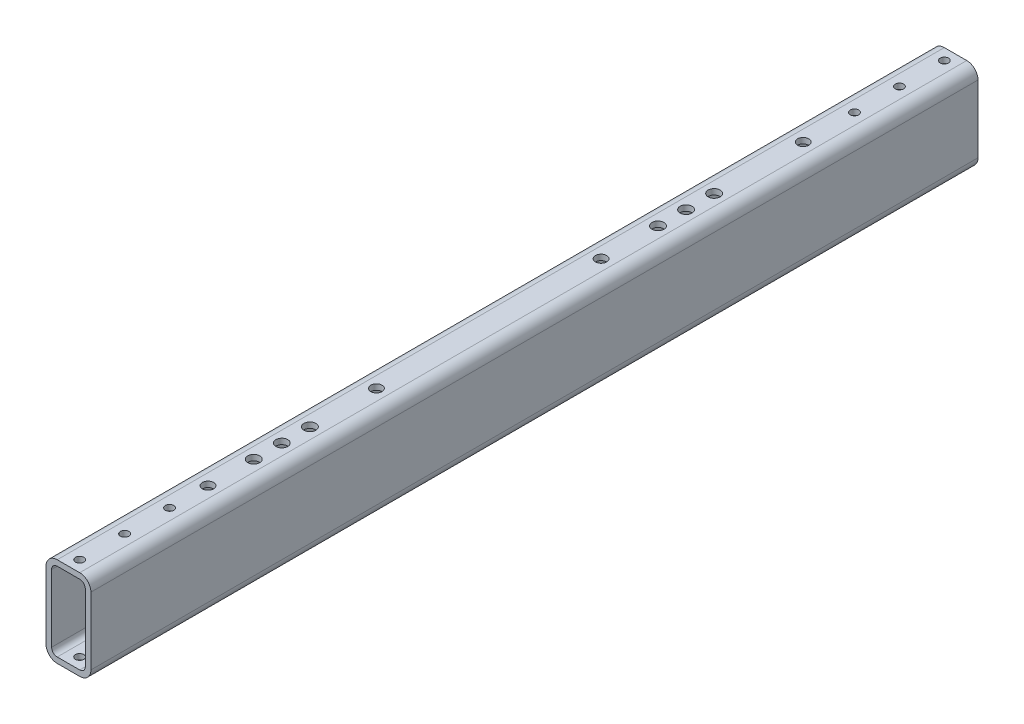
SolidWorks part; units mm, degrees
material "6061-T6 (SS)"
ref_plane "Front Plane" through (0, 0, 0) normal (0, 0, 1) x (1, 0, 0)
ref_plane "Top Plane" through (0, 0, 0) normal (0, 1, 0) x (1, 0, 0)
ref_plane "Right Plane" through (0, 0, 0) normal (1, 0, 0) x (0, 0, -1)
sketch "Sketch1" plane through (0, 0, 0) normal (0, 0, 1) x (1, 0, 0)
  line L1 (-6.35, -25.4) -> (6.35, -25.4)
  line L2 (-12.7, -19.05) -> (-12.7, 19.05)
  line L3 (-6.35, 25.4) -> (6.35, 25.4)
  line L4 (12.7, -19.05) -> (12.7, 19.05)
  line L5 (-12.7, -25.4) -> (12.7, 25.4) construction
  line L6 (-12.7, 25.4) -> (12.7, -25.4) construction
  arc A0 (-12.7, -19.05) -> (-6.35, -25.4) centre (-6.35, -19.05) ccw
  arc A1 (6.35, -25.4) -> (12.7, -19.05) centre (6.35, -19.05) ccw
  arc A2 (6.35, 25.4) -> (12.7, 19.05) centre (6.35, 19.05) cw
  arc A3 (-12.7, 19.05) -> (-6.35, 25.4) centre (-6.35, 19.05) cw
  point P0 (0, 0)
  dimension "D3" = 6.35
  dimension "D1" = 50.8
  dimension "D2" = 25.4
extrude "Extrude-Thin1" add sketch "Sketch1" along normal blind 501.65 thin thin type one direction reverse wall 3.175
hole_wizard "3/16 (0.1875) Diameter Hole1" positions "3DSketch1" profile "Sketch3" hole size "3/16" standard "ANSI Inch" end condition through all
sketch3d "3DSketch1"
  line L1 (6.35, 25.4, 0) -> (-6.35, 25.4, 0) construction
  line L6 (0, 25.4, 501.65) -> (0, 25.4, 0) construction
  line L7 (6.35, 25.4, 501.65) -> (-6.35, 25.4, 501.65) construction
  point P57 (0, 25.4, 6.35)
  point P59 (0, 25.4, 31.75)
  point P61 (0, 25.4, 57.15)
  point P63 (0, 25.4, 469.9)
  point P65 (0, 25.4, 444.5)
  point P67 (0, 25.4, 495.3)
  dimension "D1" = 25.4
  dimension "D2" = 25.4
  dimension "D3" = 6.35
  dimension "D4" = 25.4
  dimension "D5" = 25.4
  dimension "D6" = 6.35
sketch "Sketch3" plane through (0, 25.4, 495.3) normal (1, 0, 0) x (0, 0, 1)
  line L0 (0, 0) -> (0, 50.8)
  line L1 (0, 50.8) -> (2.3812, 50.8)
  line L2 (2.3812, 50.8) -> (2.3812, 0)
  line L5 (2.3812, 0) -> (0, 0)
  line L11 (0, -6.35) -> (0, 107.95) construction
  dimension "Thru Hole Dia." = 4.7625
  dimension "Thru Hole Depth" = 50.8
hole_wizard "3/16 (0.195) Diameter Hole1" positions "Sketch4" profile "Sketch5" hole size "3/16" standard "ANSI Inch" end condition up to next
sketch "Sketch4" plane through (0, -25.4, 0) normal (0, -1, 0) x (-1, 0, 0)
  point P74 (-3.175, -85.7193)
  point P78 (3.175, -111.1193)
  point P81 (-3.175, -136.5193)
  point P84 (3.175, -161.9193)
  point P87 (-3.175, -187.3193)
  point P90 (3.175, -212.7193)
  point P93 (-3.175, -238.1193)
  point P96 (3.175, -263.5193)
  point P99 (-3.175, -288.9193)
  point P102 (3.175, -314.3193)
  point P105 (-3.175, -339.7193)
  point P108 (3.175, -365.1193)
  point P111 (3.175, -415.9193)
  point P114 (-3.175, -390.5193)
sketch "Sketch5" plane through (3.175, -25.4, 85.7193) normal (1, 0, 0) x (0, 0, -1)
  line L0 (0, 0) -> (0, 3.175)
  line L1 (0, 3.175) -> (2.4765, 3.175)
  line L2 (2.4765, 3.175) -> (2.4765, 0)
  line L5 (2.4765, 0) -> (0, 0)
  line L11 (0, -6.35) -> (0, 107.95) construction
  dimension "Thru Hole Dia." = 4.953
  dimension "Thru Hole Depth" = 3.175
hole_wizard "1/4 (0.25) Diameter Hole1" positions "Sketch6" profile "Sketch7" hole size "1/4" standard "ANSI Inch"
sketch "Sketch6" plane through (0, 25.4, 0) normal (0, 1, 0) x (1, 0, 0)
  point P0 (0, -200.4645)
  point P15 (0, -422.731)
  point P23 (0, -327.481)
  point P26 (0, -86.1545)
sketch "Sketch7" plane through (0, 25.4, 200.4645) normal (1, 0, 0) x (0, 0, 1)
  line L0 (0, 0) -> (0, 27.3077)
  line L1 (0, 27.3077) -> (3.175, 25.4)
  line L2 (3.175, 25.4) -> (3.175, 0)
  line L5 (3.175, 0) -> (0, 0)
  line L10 (0, 27.3077) -> (-3.175, 25.4) construction
  line L11 (0, -6.35) -> (0, 107.95) construction
  dimension "Hole Dia." = 6.35
  dimension "Hole Depth" = 25.4
  dimension "Drill Angle" = 118
hole_wizard "1/4 Clearance Hole1" positions "Sketch17" profile "Sketch18" hole size "1/4" standard "ANSI Inch"
sketch "Sketch17" plane through (-381, 25.4, 250.825) normal (0, 1, 0) x (1, 0, 0)
  point P0 (381, 82.55)
  point P3 (381, 98.425)
  point P6 (381, 114.3)
  point P9 (381, -146.05)
  point P12 (381, -130.175)
  point P15 (381, -114.3)
  point P18 (-381, -146.05)
  point P21 (-381, -130.175)
  point P24 (-381, -114.3)
  point P27 (-381, 82.55)
  point P30 (-381, 98.425)
  point P33 (-381, 114.3)
sketch "Sketch18" plane through (0, 25.4, 168.275) normal (1, 0, 0) x (0, 0, 1)
  line L0 (0, 0) -> (0, 8.3798)
  line L1 (0, 8.3798) -> (3.3782, 6.35)
  line L2 (3.3782, 6.35) -> (3.3782, 0)
  line L3 (3.3782, 0) -> (0, 0)
  line L4 (0, 8.3798) -> (-3.3782, 6.35) construction
  line L5 (0, -6.35) -> (0, 107.95) construction
  dimension "Hole Dia." = 6.7564
  dimension "Hole Depth" = 6.35
  dimension "Drill Angle" = 118
